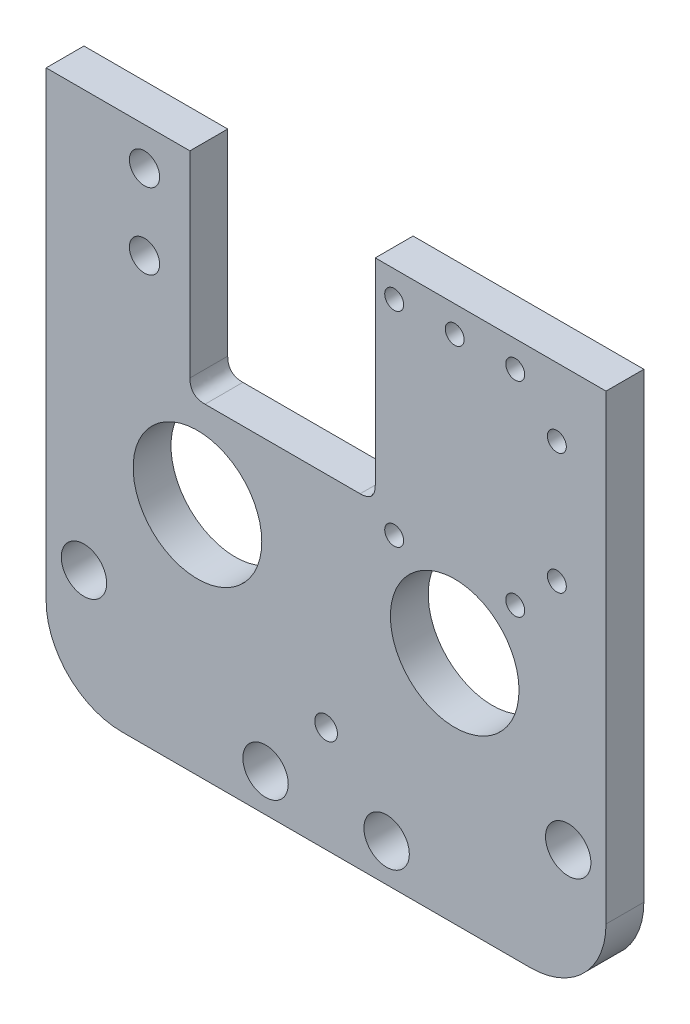
SolidWorks part; units mm, degrees
material "Stop 1060"
ref_plane "Płaszczyzna przednia" through (0, 0, 0) normal (0, 0, 1) x (1, 0, 0)
ref_plane "Płaszczyzna górna" through (0, 0, 0) normal (0, 1, 0) x (1, 0, 0)
ref_plane "Płaszczyzna prawa" through (0, 0, 0) normal (1, 0, 0) x (0, 0, -1)
sketch "Szkic1" plane through (0, 0, 0) normal (0, 0, 1) x (1, 0, 0)
  line L2 (34, 36) -> (34, -35)
  line L3 (34, -35) -> (-20, -35)
  line L6 (-20, -35) -> (-20, 36)
  line L7 (-20, 36) -> (34, 36)
  dimension "D1" = 71
  dimension "D2" = 20
  dimension "D3" = 54
  dimension "D4" = 36
extrude "Dodanie-wyciągnięcie1" add sketch "Szkic1" along normal blind 5
sketch "Szkic2" plane through (0, 0, 5) normal (0, 0, 1) x (1, 0, 0)
  line L1 (-20, 36) -> (3.5, 36)
  line L2 (-20, 36) -> (-20, 8)
  line L3 (-20, 8) -> (3.5, 8)
  line L4 (3.5, 36) -> (3.5, 8)
  dimension "D1" = 28
  dimension "D2" = 23.5
extrude "Wytnij-wyciągnięcie1" cut sketch "Szkic2" against normal blind 5
sketch "Szkic3" plane through (0, 0, 0) normal (0, 0, -1) x (-1, 0, 0)
  line L0 (-3.5, 8) -> (-3.5, 36) construction
  line L1 (-3.5, 30.5) -> (-24.5, 30.5)
  line L2 (-3.5, 30.5) -> (-3.5, 9.5)
  line L3 (-3.5, 9.5) -> (-24.5, 9.5)
  line L4 (-24.5, 30.5) -> (-24.5, 9.5)
  line L5 (-34, 36) -> (-3.5, 36) construction
  dimension "D1" = 5.5
  dimension "D2" = 21
  dimension "D3" = 21
extrude "Wytnij-wyciągnięcie2" cut sketch "Szkic3" against normal blind 3
sketch "Szkic4" plane through (0, 0, 5) normal (0, 0, 1) x (1, 0, 0)
  line L0 (3.5, 8) -> (3.5, 36) construction
  line L1 (34, 36) -> (3.5, 36) construction
  circle A0 centre (6, 32.5) radius 1.25
  circle A1 centre (14, 32.5) radius 1.25
  circle A2 centre (22, 32.5) radius 1.25
  circle A4 centre (22, 5.5) radius 1.25
  circle A5 centre (6, 5.5) radius 1.25
  circle A6 centre (27.5, 27) radius 1.25
  circle A7 centre (27.5, 11) radius 1.25
  circle A8 centre (14, 5.5) radius 1.25 [skipped]
  dimension "D1" = 2.5
  dimension "D2" = 2.5
  dimension "D4" = 3
  dimension "D6" = 8
  dimension "D8" = 5.5
  dimension "D10" = 2.5
  dimension "D3" = 3.5
  dimension "D5" = 2
  dimension "D7" = 27
  dimension "D9" = 5.5
  dimension "D11" = 2
extrude "Wytnij-wyciągnięcie3" cut sketch "Szkic4" against normal blind 5
sketch "Szkic5" plane through (0, 0, 5) normal (0, 0, 1) x (1, 0, 0)
  line L1 (-20, 8) -> (-40, 8)
  line L2 (-20, 8) -> (-20, -35)
  line L3 (-20, -35) -> (-40, -35)
  line L4 (-40, 8) -> (-40, -35)
  dimension "D1" = 20
  dimension "D2" = 43
extrude "Dodanie-wyciągnięcie2" add sketch "Szkic5" against normal blind 5
sketch "Szkic6" plane through (0, 0, 5) normal (0, 0, 1) x (1, 0, 0)
  line L0 (-40, 8) -> (-40, -35) construction
  line L1 (-40, 8) -> (3.5, 8) construction
  circle A0 centre (-20, -4) radius 8.5
  circle A1 centre (14, -4) radius 8.5
  dimension "D1" = 20
  dimension "D3" = 17
  dimension "D2" = 12
  dimension "D5" = 34
  dimension "D4" = 2
extrude "Wytnij-wyciągnięcie4" cut sketch "Szkic6" against normal blind 5
sketch "symetria" plane through (0, 0, 5) normal (0, 0, 1) x (1, 0, 0)
  line L0 (-20, -4) -> (14, -4)
  line L1 (-3, -4) -> (-3, -39)
  dimension "D1" = 35
sketch "Szkic7" plane through (0, 0, 5) normal (0, 0, 1) x (1, 0, 0)
  line L0 (-3, -4) -> (-3, -39) construction
  line L1 (-40, -35) -> (34, -35) construction
  line L2 (-3, -36.4153) -> (-3, -30)
  line L3 (-40, 8) -> (-40, -35) construction
  circle A0 centre (5, -30) radius 3
  circle A1 centre (-11, -30) radius 3
  circle A2 centre (-35, -19) radius 3
  circle A3 centre (29, -19) radius 3
  dimension "D1" = 6
  dimension "D4" = 6
  dimension "D2" = 8
  dimension "D3" = 5
  dimension "D5" = 5
  dimension "D6" = 16
extrude "Wytnij-wyciągnięcie5" cut sketch "Szkic7" against normal blind 10 contours A1 | A0 | A2 | A3 region at (5, -30, 5) region at (-11, -30, 5) region at (-35, -19, 5) region at (29, -19, 5)
fillet "Zaokrąglenie3" radius 10 2 edges at (34, -35, 2.5) (-40, -35, 2.5)
sketch "Szkic8" plane through (0, 0, 5) normal (0, 0, 1) x (1, 0, 0)
  line L1 (-40, 8) -> (-21, 8)
  line L2 (-40, 8) -> (-40, 36)
  line L3 (-40, 36) -> (-21, 36)
  line L4 (-21, 8) -> (-21, 36)
  dimension "D1" = 19
  dimension "D2" = 28
extrude "Dodanie-wyciągnięcie3" add sketch "Szkic8" against normal blind 5
fillet "Zaokrąglenie2" radius 2 2 edges at (3.5, 8, 2.5) (-21, 8, 2.5) conic rho 0.5
sketch "Szkic9" plane through (0, 0, 5) normal (0, 0, 1) x (1, 0, 0)
  line L2 (-21, 10) -> (-21, 36) construction
  line L3 (-21, 36) -> (-40, 36) construction
  circle A1 centre (-27, 31) radius 2
  circle A2 centre (-27, 21) radius 2
  dimension "D1" = 6
  dimension "D2" = 6
  dimension "D3" = 4
  dimension "D4" = 4
  dimension "D6" = 10
  dimension "D5" = 5
extrude "Wytnij-wyciągnięcie6" cut sketch "Szkic9" against normal blind 10
sketch "Szkic10" plane through (0, 0, 5) normal (0, 0, 1) x (1, 0, 0)
  line L0 (-3, -4) -> (-3, -39) construction
  line L1 (-30, -35) -> (24, -35) construction
  circle A0 centre (-3, -21) radius 1.5
  dimension "D1" = 14
  dimension "D2" = 3
extrude "Wytnij-wyciągnięcie7" cut sketch "Szkic10" against normal blind 10
fillet "Zaokrąglenie4" radius 2 2 edges at (24.5, 9.5, 1.5) (24.5, 30.5, 1.5)
